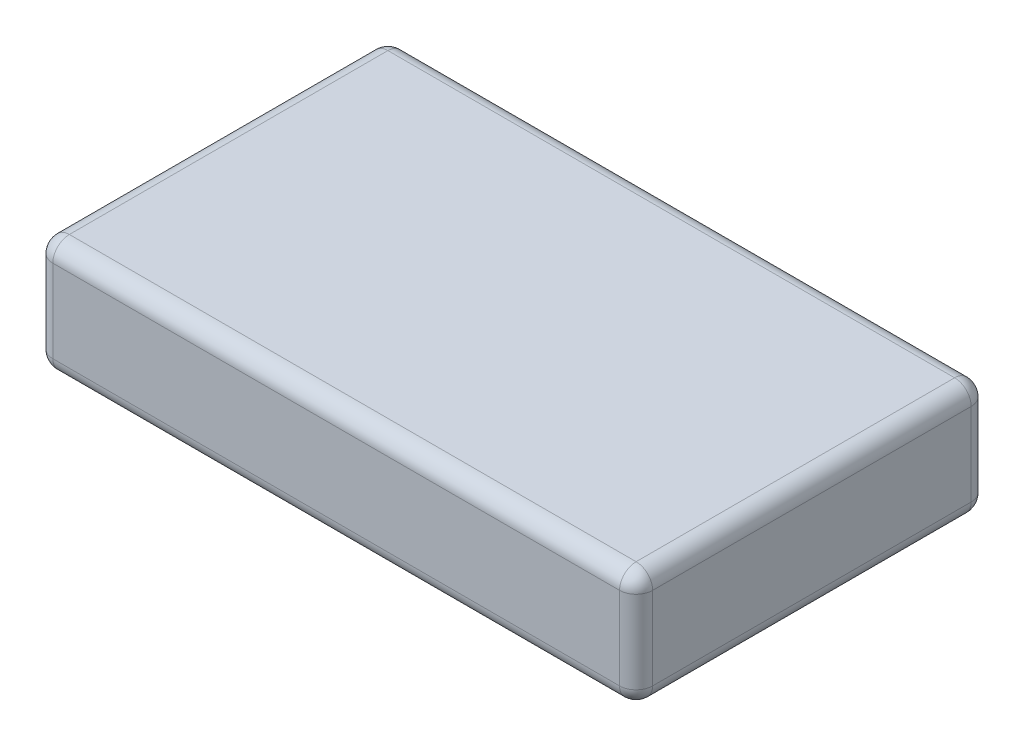
SolidWorks part; units mm, degrees
ref_plane "Front Plane" through (0, 0, 0) normal (0, 0, 1) x (1, 0, 0)
ref_plane "Top Plane" through (0, 0, 0) normal (0, 1, 0) x (1, 0, 0)
ref_plane "Right Plane" through (0, 0, 0) normal (1, 0, 0) x (0, 0, -1)
sketch "Çizim1" plane through (0, 0, 0) normal (0, 1, 0) x (1, 0, 0)
  line L1 (-72.5, -42.5) -> (72.5, -42.5)
  line L2 (-72.5, -42.5) -> (-72.5, 42.5)
  line L3 (-72.5, 42.5) -> (72.5, 42.5)
  line L4 (72.5, -42.5) -> (72.5, 42.5)
  line L5 (-72.5, -42.5) -> (72.5, 42.5) construction
  line L6 (-72.5, 42.5) -> (72.5, -42.5) construction
  point P0 (0, 0)
  dimension "D1" = 145
  dimension "D2" = 85
extrude "Yükseklik-Ekstrüzyon1" add sketch "Çizim1" along normal blind 28
sketch "Çizim2" plane through (-72.5, 0, 0) normal (-1, 0, 0) x (0, 0, 1)
  line L0 (-42.5, 28) -> (42.5, 28) construction
  line L1 (-42.5, 0) -> (42.5, 0) construction
  line L2 (42.5, 28) -> (42.5, 0) construction
  circle A0 centre (25.2, 12.4) radius 2.75
  circle A1 centre (25.2, 12.4) radius 0.5
  dimension "D1" = 15.6
  dimension "D2" = 12.4
  dimension "D3" = 17.3
extrude "Kes-Ekstrüzyon1" cut sketch "Çizim2" against normal blind 9
sketch "Çizim3" plane through (-72.5, 0, 0) normal (-1, 0, 0) x (0, 0, 1)
  line L0 (-42.5, 28) -> (42.5, 28) construction
  line L1 (-28.875, 18.9188) -> (-24.375, 18.9188)
  line L2 (-28.875, 18.9188) -> (-28.875, 6.9188)
  line L3 (-28.875, 6.9188) -> (-24.375, 6.9188)
  line L4 (-24.375, 18.9188) -> (-24.375, 6.9188)
  line L5 (-28.875, 18.9188) -> (-24.375, 6.9188) construction
  line L6 (-28.875, 6.9188) -> (-24.375, 18.9188) construction
  line L7 (-42.5, 28) -> (-42.5, 0) construction
  line L9 (-26.7808, 17.8366) -> (-24.7808, 17.8366)
  line L10 (-26.7808, 17.8366) -> (-26.7808, 8.0009)
  line L11 (-26.7808, 8.0009) -> (-24.7808, 8.0009)
  line L12 (-24.7808, 17.8366) -> (-24.7808, 8.0009)
  line L13 (-26.7808, 17.8366) -> (-24.7808, 8.0009) construction
  line L14 (-26.7808, 8.0009) -> (-24.7808, 17.8366) construction
  line L15 (-28.0464, 16.4188) -> (-27.1808, 16.4188)
  line L16 (-28.0464, 16.4188) -> (-28.0464, 9.4188)
  line L17 (-28.0464, 9.4188) -> (-27.1808, 9.4188)
  line L18 (-27.1808, 16.4188) -> (-27.1808, 9.4188)
  line L19 (-28.0464, 16.4188) -> (-27.1808, 9.4188) construction
  line L20 (-28.0464, 9.4188) -> (-27.1808, 16.4188) construction
  point P0 (-26.625, 12.9187)
  point P9 (-25.7808, 12.9187)
  point P14 (-27.6136, 12.9187)
  dimension "D1" = 12
  dimension "D2" = 4.5
  dimension "D3" = 15.0813
  dimension "D4" = 15.875
  dimension "D5" = 7
  dimension "D6" = 0
  dimension "D7" = 0.4
  dimension "D8" = 2
  dimension "D9" = 0
extrude "Kes-Ekstrüzyon2" cut sketch "Çizim3" against normal blind 9
fillet "Radyus3" radius 4 4 edges at (0, 28, 42.5) (72.5, 28, 0) (0, 28, -42.5) (-72.5, 28, 0)
fillet "Radyus6" radius 4 4 edges at (0, 0, -42.5) (72.5, 0, 0) (0, 0, 42.5) (-72.5, 0, 0)
fillet "Radyus7" radius 4 12 edges at (71.3284, 26.8284, -41.3284) (71.3284, 1.1716, -41.3284) (71.3284, 26.8284, 41.3284) (71.3284, 1.1716, 41.3284) (-71.3284, 26.8284, 41.3284) (-71.3284, 1.1716, 41.3284) (-71.3284, 26.8284, -41.3284) (-71.3284, 1.1716, -41.3284) (72.5, 14, -42.5) (72.5, 14, 42.5) (-72.5, 14, 42.5) (-72.5, 14, -42.5)
